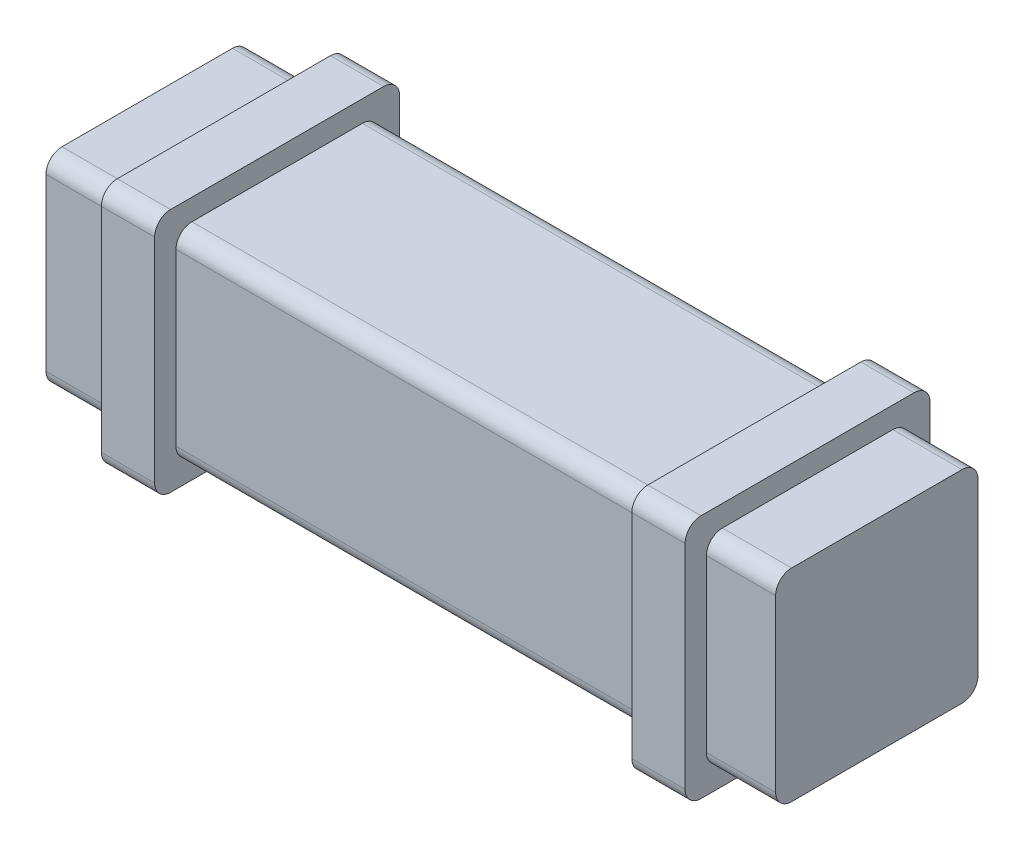
SolidWorks part; units mm, degrees
ref_plane "정면" through (0, 0, 0) normal (1, 0, 0) x (0, 1, 0)
ref_plane "윗면" through (0, 0, 0) normal (0, 0, 1) x (0, 1, 0)
ref_plane "우측면" through (0, 0, 0) normal (0, 1, 0) x (-1, 0, 0)
sketch "스케치1" plane through (0, 0, 0) normal (1, 0, 0) x (0, 1, 0)
  line L1 (-16, 19) -> (16, 19)
  line L2 (-19, 16) -> (-19, -16)
  line L3 (-16, -19) -> (16, -19)
  line L4 (19, 16) -> (19, -16)
  line L5 (-19, 19) -> (19, -19) construction
  line L6 (-19, -19) -> (19, 19) construction
  arc A0 (-19, -16) -> (-16, -19) centre (-16, -16) ccw
  arc A1 (16, -19) -> (19, -16) centre (16, -16) ccw
  arc A2 (16, 19) -> (19, 16) centre (16, 16) cw
  arc A3 (-16, 19) -> (-19, 16) centre (-16, 16) ccw
  point P0 (0, 0)
  dimension "D3" = 3
  dimension "D1" = 38
  dimension "D2" = 38
extrude "보스-돌출1" add sketch "스케치1" along normal blind 137
sketch "스케치2" plane through (0, 0, 0) normal (-1, 0, 0) x (0, -1, 0)
  line L1 (-20, 23) -> (20, 23)
  line L2 (-23, 20) -> (-23, -20)
  line L3 (-20, -23) -> (20, -23)
  line L4 (23, 20) -> (23, -20)
  line L5 (-23, 23) -> (23, -23) construction
  line L6 (-23, -23) -> (23, 23) construction
  arc A0 (-23, -20) -> (-20, -23) centre (-20, -20) ccw
  arc A1 (20, -23) -> (23, -20) centre (20, -20) ccw
  arc A2 (20, 23) -> (23, 20) centre (20, 20) cw
  arc A3 (-20, 23) -> (-23, 20) centre (-20, 20) ccw
  point P0 (0, 0)
  dimension "D3" = 3
  dimension "D1" = 46
  dimension "D2" = 46
extrude "보스-돌출2" add sketch "스케치2" against normal blind 10 from offset 14.4 offset against normal yes
extrude "보스-돌출3" add sketch "스케치2<2>" against normal blind 10 from offset 114 offset against normal yes
sketch "스케치2<2>" plane through (0, 0, 0) normal (-1, 0, 0) x (0, -1, 0) same geometry as "스케치2"
